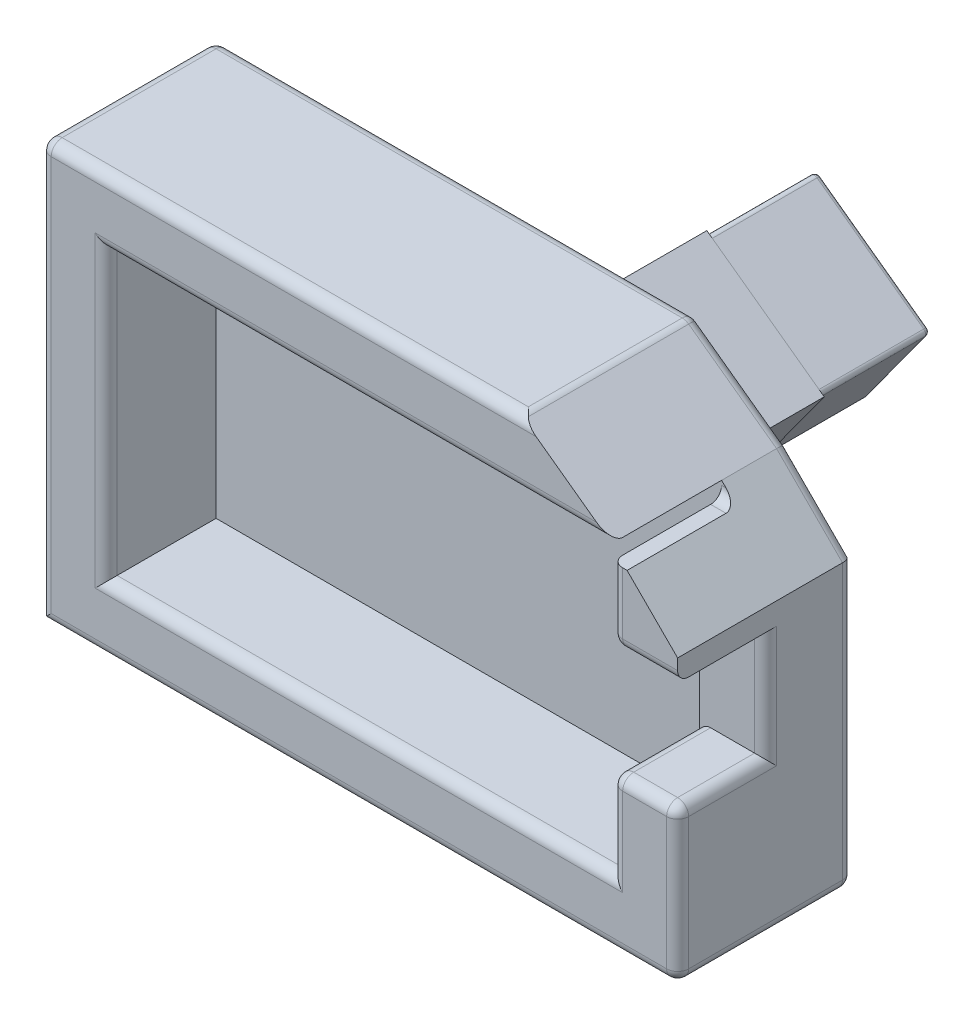
SolidWorks part; units mm, degrees
ref_plane "Front Plane" through (0, 0, 0) normal (0, 0, 1) x (1, 0, 0)
ref_plane "Top Plane" through (0, 0, 0) normal (0, 1, 0) x (1, 0, 0)
ref_plane "Right Plane" through (0, 0, 0) normal (1, 0, 0) x (0, 0, -1)
sketch "Sketch1" plane through (0, 0, 0) normal (0, 0, 1) x (1, 0, 0)
  line L0 (14.5, -9.5) -> (-14.5, -9.5)
  line L1 (11.5, -6.5) -> (-11.5, -6.5) construction
  line L2 (11.5, -6.5) -> (11.5, 6.5) construction
  line L3 (11.5, 6.5) -> (-11.5, 6.5) construction
  line L4 (-11.5, -6.5) -> (-11.5, 6.5) construction
  line L5 (11.5, -6.5) -> (-11.5, 6.5) construction
  line L6 (11.5, 6.5) -> (-11.5, -6.5) construction
  line L7 (-14.5, -9.5) -> (-14.5, 9.5)
  line L13 (14.5, -9.5) -> (14.5, 9.5) construction
  line L14 (14.5, -9.5) -> (-14.5, -9.5) construction
  line L15 (11.5, 6.5) -> (7.3709, 9.5)
  line L16 (11.5, 6.5) -> (14.5, 3.5)
  line L17 (14.5, 3.5) -> (14.5, -9.5)
  line L18 (-14.5, 9.5) -> (7.3709, 9.5)
  line L19 (14.5, 9.5) -> (-14.5, 9.5) construction
  point P0 (0, 0)
  dimension "D1" = 13
  dimension "D2" = 23
  dimension "D4" = 45
  dimension "D5" = 36
  dimension "D3" = 3
extrude "Boss-Extrude1" add sketch "Sketch1" along normal blind 3
sketch "Sketch2" plane through (0, 0, 3) normal (0, 0, 1) x (1, 0, 0)
  line L1 (11.5, -6.5) -> (-11.5, -6.5)
  line L3 (11.5, 6.5) -> (-11.5, 6.5)
  line L4 (-11.5, -6.5) -> (-11.5, 6.5)
  line L5 (11.5, -6.5) -> (-11.5, 6.5) construction
  line L6 (11.5, 6.5) -> (-11.5, -6.5) construction
  line L11 (14.5, -9.5) -> (-14.5, 9.5) construction
  line L12 (14.5, 9.5) -> (-14.5, -9.5) construction
  line L15 (7.3709, -9.5) -> (7.3709, 9.5) construction
  line L16 (7.3709, 9.5) -> (11.5, 6.5)
  line L18 (-14.5, -9.5) -> (14.5, -9.5)
  line L19 (14.5, -9.5) -> (14.5, 3.5)
  line L20 (14.5, -9.5) -> (14.5, 3.5) construction
  line L21 (14.5, 3.5) -> (12.2, 5.8)
  line L22 (12.2, 5.8) -> (11.5, 5.8)
  line L23 (11.5, -6.5) -> (11.5, 5.8)
  line L27 (-14.5, 9.5) -> (7.3709, 9.5)
  line L28 (-14.5, 9.5) -> (-14.5, -9.5)
  point P0 (0, 0)
  point P7 (0, 0)
  dimension "D4" = 13
  dimension "D5" = 2.3
  dimension "D6" = 45
extrude "Boss-Extrude2" add sketch "Sketch2" along normal blind 5
sketch "Sketch3" plane through (0, 0, 0) normal (0, 0, -1) x (-1, 0, 0)
  line L0 (0, 0) -> (7.0906, 0) construction
  line L1 (1.1194, 3.9035) -> (4.0583, -0.1416)
  line L2 (1.1194, 3.9035) -> (-4.0583, 0.1416)
  line L3 (-4.0583, 0.1416) -> (-1.1194, -3.9035)
  line L4 (4.0583, -0.1416) -> (-1.1194, -3.9035)
  line L5 (1.1194, 3.9035) -> (-1.1194, -3.9035) construction
  line L6 (-4.0583, 0.1416) -> (4.0583, -0.1416) construction
  line L7 (0, 0) -> (3.0495, -4.1972) construction
  line L8 (-4.1686, 0.1233) -> (1.1709, 4.0027)
  line L9 (1.1709, 4.0027) -> (4.1686, -0.1233)
  line L10 (4.1686, -0.1233) -> (-1.1709, -4.0027)
  line L11 (-1.1709, -4.0027) -> (-4.1686, 0.1233)
  point P0 (0, 0)
  point P9 (7.0906, -0.0829)
  dimension "D1" = 54
  dimension "D2" = 6.4
  dimension "D3" = 5.188
  dimension "D4" = 5
  dimension "D5" = 5.1
  dimension "D6" = 2.55
  dimension "D7" = 6.6
  dimension "D8" = 3.3
sketch "Sketch4" plane through (14.5, 0, 0) normal (1, 0, 0) x (0, 0, -1)
  line L1 (-8, 2.5) -> (-8, -2.5)
  line L2 (-4, -2.5) -> (-8, -2.5)
  line L3 (-4, -2.5) -> (-4, 2.5)
  line L4 (-4, 2.5) -> (-8, 2.5)
  line L5 (-8, -9.5) -> (0, -9.5) construction
  line L6 (-8, -9.5) -> (-8, 3.5) construction
  dimension "D3" = 5
  dimension "D4" = 4
  dimension "D5" = 7
extrude "Cut-Extrude1" cut sketch "Sketch4" against normal blind 8
fillet "Fillet2" radius 0.5 25 edges at (-14.5, 0, 0) (-14.5, 9.5, 4) (-3.5646, 9.5, 0) (7.3709, 9.5, 4) (9.4354, 8, 0) (13, 5, 0) (0, -9.5, 0) (14.5, -3, 0) (14.5, -9.5, 4) (11.5, 2.5, 6) (11.85, 5.8, 3) (13, 2.5, 8) (14.5, 0, 4) (14.5, -2.5, 6) (11.5, -2.5, 6) (13, -2.5, 8) (14.5, -6, 8) (0, -9.5, 8) (-14.5, 0, 8) (-3.5646, 9.5, 8) (-11.5, 0, 8) (0, -6.5, 8) (11.5, -4.5, 8) (0, 6.5, 8) (11.5, 4.15, 8)
extrude "Boss-Extrude4" add sketch "Sketch3" along normal blind 14 contours L4 L1 L2 L3 region at (0, 0, 0)
extrude "Boss-Extrude5" add sketch "Sketch3<5>" along normal blind 9
sketch "Sketch3<5>" plane through (0, 0, 0) normal (0, 0, -1) x (-1, 0, 0) same geometry as "Sketch3"
fillet "Fillet3" radius 0.2 8 edges at (-1.1194, 3.9035, -11.5) (-2.5889, 1.8809, -14) (1.4695, 2.0225, -14) (-1.4695, -2.0225, -14) (2.5889, -1.8809, -14) (4.0583, 0.1416, -11.5) (-4.0583, -0.1416, -11.5) (1.1194, -3.9035, -11.5)
